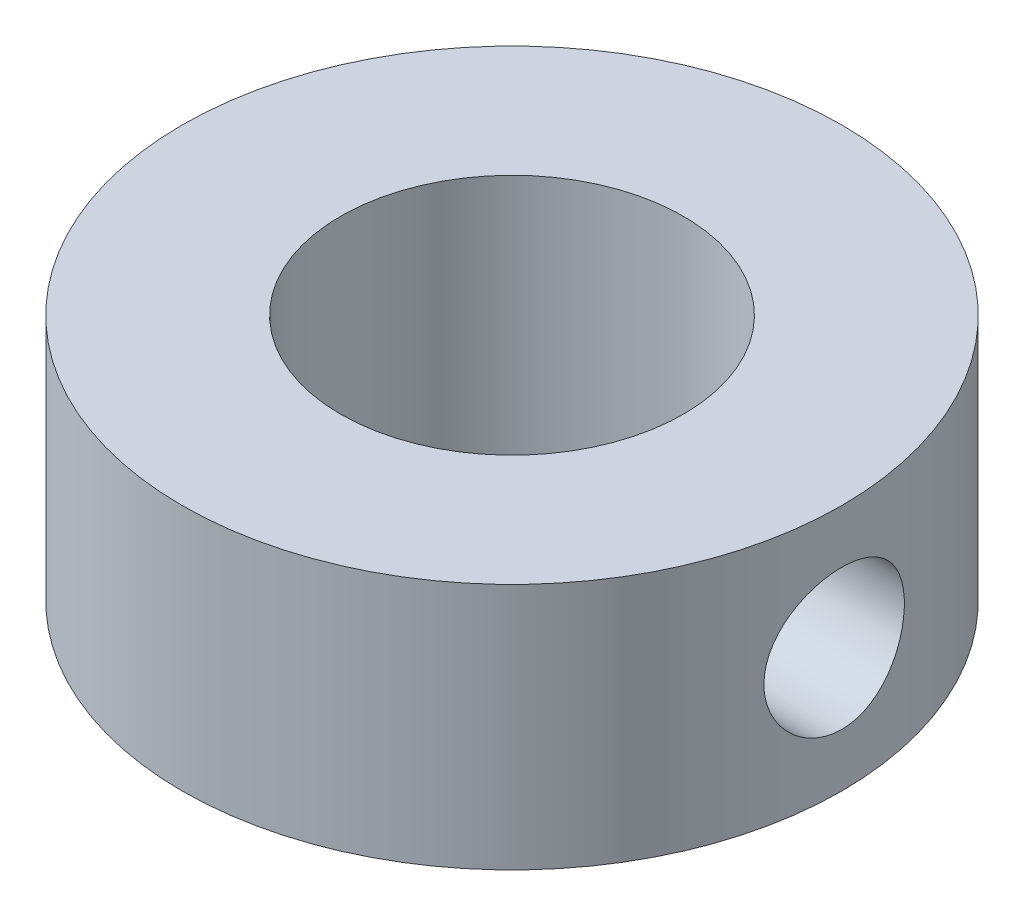
SolidWorks part; units mm, degrees
material "Polycarbonate"
ref_plane "Front Plane" through (0, 0, 0) normal (0, 0, 1) x (1, 0, 0)
ref_plane "Top Plane" through (0, 0, 0) normal (0, 1, 0) x (1, 0, 0)
ref_plane "Right Plane" through (0, 0, 0) normal (1, 0, 0) x (0, 0, -1)
sketch "Sketch1" plane through (0, 0, 0) normal (0, 1, 0) x (1, 0, 0)
  circle A0 centre (0, 0) radius 3.302
  circle A1 centre (0, 0) radius 6.35
  dimension "D1" = 6.604
  dimension "D2" = 12.7
extrude "Boss-Extrude1" add sketch "Sketch1" along normal blind 4.7625
hole_wizard "#6-32 Tapped Hole1" positions "Sketch2" profile "Sketch3" tap size "#6-32" standard "ANSI Inch" end condition through all
sketch "Sketch2" plane through (0, 0, 0) normal (1, 0, 0) x (0, 0, -1)
  line L0 (6.35, 4.7625) -> (-6.35, 4.7625) construction
  line L1 (-6.35, 0) -> (6.35, 0) construction
  line L2 (6.35, 4.7625) -> (-6.35, 4.7625) construction
  line L3 (-6.35, 0) -> (6.35, 0) construction
  line L4 (0, 4.7625) -> (0, 0) construction
  point P0 (0, 2.3813)
  point P11 (0, 3.175)
sketch "Sketch3" plane through (0, 2.3813, 0) normal (0, 1, 0) x (0, 0, 1)
  line L0 (0, 0) -> (0, 6.35)
  line L1 (0, 6.35) -> (1.3525, 6.35)
  line L2 (1.3525, 6.35) -> (1.3525, 0)
  line L5 (1.3525, 0) -> (0, 0)
  line L11 (0, -6.35) -> (0, 107.95) construction
  dimension "Thru Tap Drill Dia." = 2.7051
  dimension "Thru Tap Drill Depth" = 6.35
cosmetic thread "Hole Thread1"
